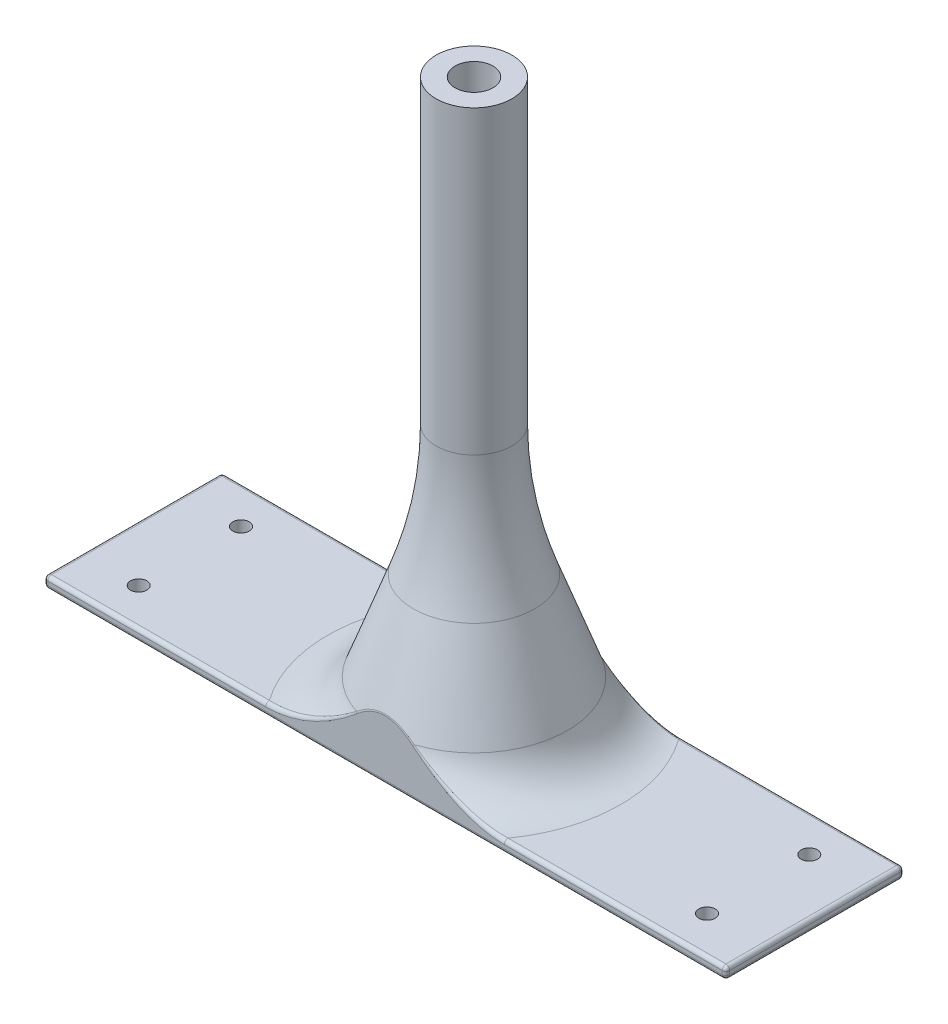
SolidWorks part; units mm, degrees
ref_plane "Alzado" through (0, 0, 0) normal (0, 0, 1) x (1, 0, 0)
ref_plane "Planta" through (0, 0, 0) normal (0, 1, 0) x (1, 0, 0)
ref_plane "Vista lateral" through (0, 0, 0) normal (1, 0, 0) x (0, 0, -1)
sketch "Croquis1" plane through (0, 0, 0) normal (0, 1, 0) x (1, 0, 0)
  circle A0 centre (0, 0) radius 10
  dimension "D1" = 20
extrude "Saliente-Extruir1" add sketch "Croquis1" along normal blind 150
sketch "Croquis5" plane through (0, 150, 0) normal (0, -1, 0) x (1, 0, 0)
  circle A0 centre (0, 0) radius 5
  dimension "D1" = 10
extrude "Cortar-Extruir1" cut sketch "Croquis5" against normal through all both and the other way through all
sketch "Croquis6" plane through (0, 0, 0) normal (0, 1, 0) x (1, 0, 0)
  line L0 (-90, 13.5) -> (-75, 13.5) construction
  line L1 (-90, 23.5) -> (90, 23.5)
  line L2 (-90, 23.5) -> (-90, -23.5)
  line L3 (-90, -23.5) -> (90, -23.5)
  line L4 (90, 23.5) -> (90, -23.5)
  line L5 (-90, 23.5) -> (90, -23.5) construction
  line L6 (-90, -23.5) -> (90, 23.5) construction
  line L7 (-75, 13.5) -> (-75, 23.5) construction
  line L8 (-18.619, 0) -> (0, 0) construction
  line L9 (0, 0) -> (0, 19.4113) construction
  circle A0 centre (-75, 13.5) radius 2.15
  circle A1 centre (75, 13.5) radius 2.15
  circle A2 centre (75, -13.5) radius 2.15
  circle A3 centre (-75, -13.5) radius 2.15
  circle A4 centre (0, 0) radius 5
  point P0 (0, 0)
  dimension "D5" = 4.3
  dimension "D1" = 47
  dimension "D2" = 180
  dimension "D3" = 15
  dimension "D4" = 10
  dimension "D6" = 75
  dimension "D7" = 13.5
extrude "Saliente-Extruir2" add sketch "Croquis6" along normal blind 3
chamfer "Chaflán1" distance 50 angle 20 1 edges at (0, 3, 10) first distance on face at (0, 3, 10)
fillet "Redondeo1" radius 15 2 edges at (-28.1985, 3, 0) (28.1985, 3, 0)
fillet "Redondeo2" radius 1 20 edges at (20.3072, 5.0933, -23.5) (0.5986, 15.8881, -23.5) (90, 1.5, -23.5) (60.375, 3, -23.5) (90, 0, 0) (0, 0, -23.5) (-23.2501, 4.1023, -23.5) (90, 3, 0) (90, 1.5, 23.5) (0, 0, 23.5) (-90, 0, 0) (-90, 1.5, -23.5) (-60.375, 3, -23.5) (60.375, 3, 23.5) (-90, 1.5, 23.5) (-90, 3, 0) (23.2501, 4.1023, 23.5) (-60.375, 3, 23.5) (-0.5986, 15.8881, 23.5) (-20.3072, 5.0933, 23.5)
sketch "Croquis7" plane through (0, 0, 0) normal (0, -1, 0) x (1, 0, 0)
  circle A0 centre (0, 0) radius 5
  circle A1 centre (0, 0) radius 15.85
  dimension "D1" = 31.7
  dimension "D2" = 10
extrude "Cortar-Extruir2" cut sketch "Croquis7" against normal blind 10
fillet "Redondeo5" radius 100 1 edges at (0, 53, 10)
